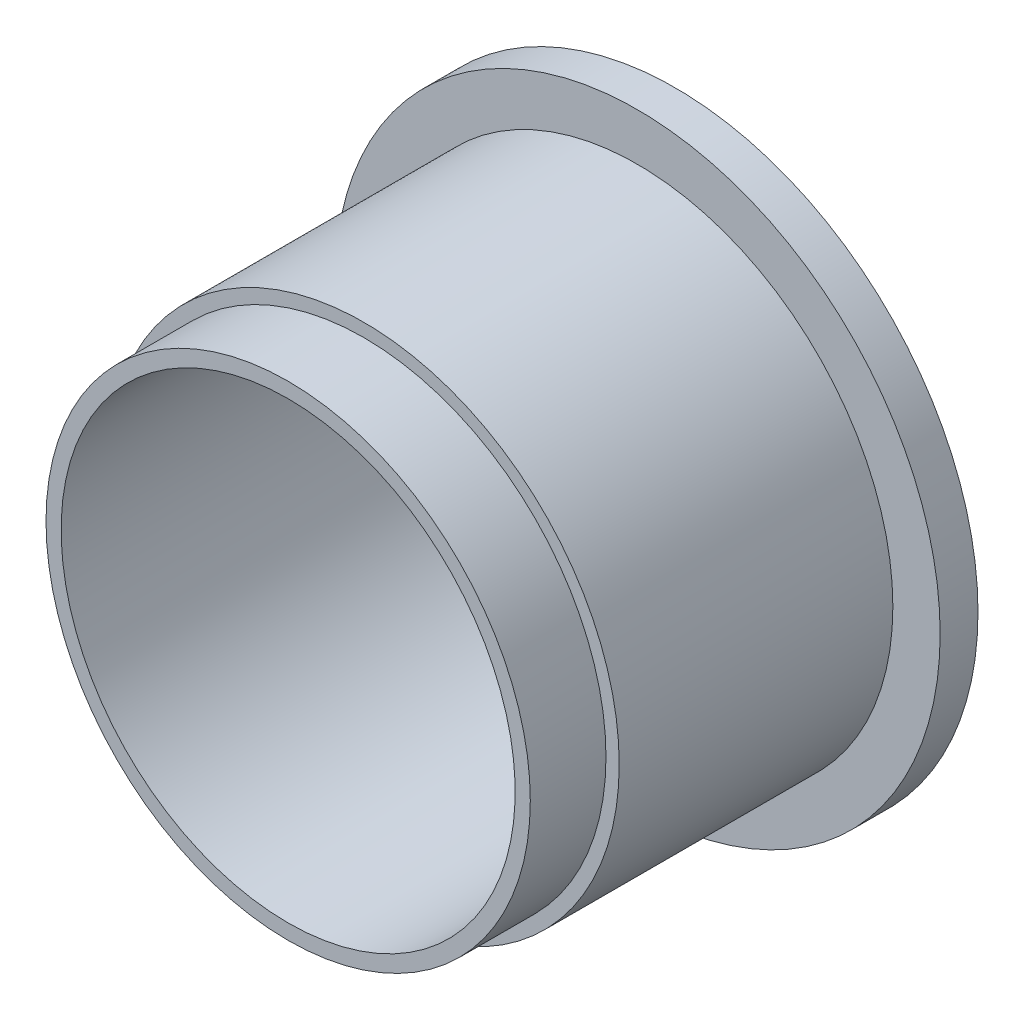
SolidWorks part; units mm, degrees
ref_plane "Front Plane" through (0, 0, 0) normal (0, 0, 1) x (1, 0, 0)
ref_plane "Top Plane" through (0, 0, 0) normal (0, 1, 0) x (1, 0, 0)
ref_plane "Right Plane" through (0, 0, 0) normal (1, 0, 0) x (0, 0, -1)
sketch "Sketch1" plane through (0, 0, 0) normal (0, 0, 1) x (1, 0, 0)
  circle A0 centre (0, 0) radius 25.4
  circle A1 centre (0, 0) radius 19.05
  dimension "D1" = 50.8
  dimension "D2" = 38.1
extrude "Boss-Extrude1" add sketch "Sketch1" along normal up to surface (32.4869 mm away)
sketch "Sketch2" plane through (0, 0, 32.4869) normal (0, 0, 1) x (1, 0, 0)
  circle A0 centre (0, 0) radius 20.32
  circle A3 centre (0, 0) radius 19.05 construction
  dimension "D1" = 1.27
extrude "Cut-Extrude1" cut sketch "Sketch2" against normal blind 6.35 flip side to cut
sketch "Sketch3" plane through (0, 0, 26.1369) normal (0, 0, 1) x (1, 0, 0)
  circle A0 centre (0, 0) radius 21.4313
  circle A2 centre (0, 0) radius 19.05 construction
  dimension "D1" = 2.3813
extrude "Cut-Extrude3" cut sketch "Sketch3" against normal offset from surface (22.9619 mm away) 3.175 flip side to cut up to face at (25.4, 0, 0)
